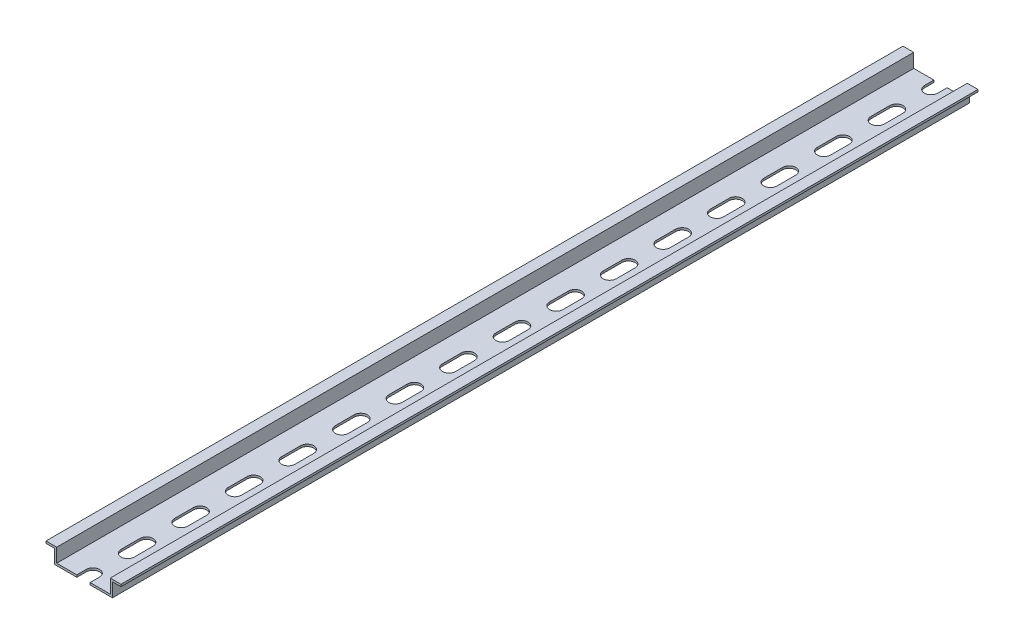
SolidWorks part; units mm, degrees
ref_plane "Front Plane" through (0, 0, 0) normal (0, 0, 1) x (1, 0, 0)
ref_plane "Top Plane" through (0, 0, 0) normal (0, 1, 0) x (1, 0, 0)
ref_plane "Right Plane" through (0, 0, 0) normal (1, 0, 0) x (0, 0, -1)
ref_plane "Plane4" through (0, -44.0251, 0) normal (0, 1, 0) x (1, 0, 0)
sketch "Sketch1" plane through (0, -44.0251, 0) normal (0, 1, 0) x (1, 0, 0)
  line L0 (139.3389, -100) -> (139.3389, 1900)
  line L1 (139.3389, 1900) -> (104.3389, 1900)
  line L2 (104.3389, 1900) -> (104.3389, -100)
  line L3 (104.3389, -100) -> (139.3389, -100)
extrude "Boss-Extrude1" add sketch "Sketch1" against normal blind 7.5
sketch "Sketch2" plane through (0, 0, -1900) normal (0, 0, -1) x (-1, 0, 0)
  line L0 (-134.3389, -44.0251) -> (-134.3389, -50.5251)
  line L1 (-134.3389, -50.5251) -> (-109.3389, -50.5251)
  line L2 (-109.3389, -50.5251) -> (-109.3389, -44.0251)
  line L3 (-109.3389, -44.0251) -> (-134.3389, -44.0251)
extrude "Cut-Extrude1" cut sketch "Sketch2" against normal through all
sketch "Sketch3" plane through (0, -51.5251, 0) normal (0, -1, 0) x (1, 0, 0)
  line L0 (118.7389, -1900) -> (124.9389, -1900)
  line L1 (124.9389, -1900) -> (124.9389, -1895.6)
  line L2 (118.7389, -1895.6) -> (118.7389, -1900)
  arc A0 (124.9389, -1895.6) -> (118.7389, -1895.6) centre (121.8389, -1895.6) ccw
extrude "Cut-Extrude2" cut sketch "Sketch3" against normal through all
sketch "Sketch4" plane through (0, 0, -1900) normal (0, 0, -1) x (-1, 0, 0)
  line L0 (-104.3389, -45.0251) -> (-108.3389, -45.0251)
  line L1 (-108.3389, -45.0251) -> (-108.3389, -51.5251)
  line L2 (-108.3389, -51.5251) -> (-104.3389, -51.5251)
  line L3 (-104.3389, -51.5251) -> (-104.3389, -45.0251)
extrude "Cut-Extrude3" cut sketch "Sketch4" against normal through all
sketch "Sketch5" plane through (0, 0, -1900) normal (0, 0, -1) x (-1, 0, 0)
  line L0 (-135.3389, -45.0251) -> (-139.3389, -45.0251)
  line L1 (-139.3389, -45.0251) -> (-139.3389, -51.5251)
  line L2 (-139.3389, -51.5251) -> (-135.3389, -51.5251)
  line L3 (-135.3389, -51.5251) -> (-135.3389, -45.0251)
extrude "Cut-Extrude4" cut sketch "Sketch5" against normal through all
sketch "Sketch6" plane through (0, -51.5251, 0) normal (0, -1, 0) x (1, 0, 0)
  line L0 (118.7389, 100) -> (118.7389, 95.6)
  line L1 (124.9389, 95.6) -> (124.9389, 100)
  line L2 (124.9389, 100) -> (118.7389, 100)
  arc A0 (118.7389, 95.6) -> (124.9389, 95.6) centre (121.8389, 95.6) ccw
extrude "Cut-Extrude5" cut sketch "Sketch6" against normal through all
sketch "Sketch7" plane through (0, -50.5251, 0) normal (0, 1, 0) x (-1, 0, 0)
  line L0 (-118.7389, -54.4) -> (-118.7389, -45.6)
  line L1 (-124.9389, -45.6) -> (-124.9389, -54.4)
  arc A0 (-118.7389, -45.6) -> (-124.9389, -45.6) centre (-121.8389, -45.6) ccw
  arc A1 (-124.9389, -54.4) -> (-118.7389, -54.4) centre (-121.8389, -54.4) ccw
extrude "Cut-Extrude6" cut sketch "Sketch7" against normal through all
sketch "Sketch8" plane through (0, -50.5251, 0) normal (0, 1, 0) x (-1, 0, 0)
  line L0 (-124.9389, 29.4) -> (-124.9389, 20.6)
  line L1 (-118.7389, 20.6) -> (-118.7389, 29.4)
  arc A0 (-118.7389, 29.4) -> (-124.9389, 29.4) centre (-121.8389, 29.4) ccw
  arc A1 (-124.9389, 20.6) -> (-118.7389, 20.6) centre (-121.8389, 20.6) ccw
extrude "Cut-Extrude7" cut sketch "Sketch8" against normal through all
sketch "Sketch9" plane through (0, -50.5251, 0) normal (0, 1, 0) x (-1, 0, 0)
  line L0 (-118.7389, -1829.4) -> (-118.7389, -1820.6)
  line L1 (-124.9389, -1820.6) -> (-124.9389, -1829.4)
  arc A0 (-118.7389, -1820.6) -> (-124.9389, -1820.6) centre (-121.8389, -1820.6) ccw
  arc A1 (-124.9389, -1829.4) -> (-118.7389, -1829.4) centre (-121.8389, -1829.4) ccw
extrude "Cut-Extrude8" cut sketch "Sketch9" against normal through all
sketch "Sketch10" plane through (0, -50.5251, 0) normal (0, 1, 0) x (-1, 0, 0)
  line L0 (-118.7389, -1529.4) -> (-118.7389, -1520.6)
  line L1 (-124.9389, -1520.6) -> (-124.9389, -1529.4)
  arc A0 (-118.7389, -1520.6) -> (-124.9389, -1520.6) centre (-121.8389, -1520.6) ccw
  arc A1 (-124.9389, -1529.4) -> (-118.7389, -1529.4) centre (-121.8389, -1529.4) ccw
extrude "Cut-Extrude9" cut sketch "Sketch10" against normal through all
sketch "Sketch11" plane through (0, -50.5251, 0) normal (0, 1, 0) x (-1, 0, 0)
  line L0 (-124.9389, -1120.6) -> (-124.9389, -1129.4)
  line L1 (-118.7389, -1129.4) -> (-118.7389, -1120.6)
  arc A0 (-124.9389, -1129.4) -> (-118.7389, -1129.4) centre (-121.8389, -1129.4) ccw
  arc A1 (-118.7389, -1120.6) -> (-124.9389, -1120.6) centre (-121.8389, -1120.6) ccw
extrude "Cut-Extrude10" cut sketch "Sketch11" against normal through all
sketch "Sketch12" plane through (0, -50.5251, 0) normal (0, 1, 0) x (-1, 0, 0)
  line L0 (-118.7389, -404.4) -> (-118.7389, -395.6)
  line L1 (-124.9389, -395.6) -> (-124.9389, -404.4)
  arc A0 (-124.9389, -404.4) -> (-118.7389, -404.4) centre (-121.8389, -404.4) ccw
  arc A1 (-118.7389, -395.6) -> (-124.9389, -395.6) centre (-121.8389, -395.6) ccw
extrude "Cut-Extrude11" cut sketch "Sketch12" against normal through all
sketch "Sketch13" plane through (0, -50.5251, 0) normal (0, 1, 0) x (-1, 0, 0)
  line L0 (-118.7389, -304.4) -> (-118.7389, -295.6)
  line L1 (-124.9389, -295.6) -> (-124.9389, -304.4)
  arc A0 (-118.7389, -295.6) -> (-124.9389, -295.6) centre (-121.8389, -295.6) ccw
  arc A1 (-124.9389, -304.4) -> (-118.7389, -304.4) centre (-121.8389, -304.4) ccw
extrude "Cut-Extrude12" cut sketch "Sketch13" against normal through all
sketch "Sketch14" plane through (0, -50.5251, 0) normal (0, 1, 0) x (-1, 0, 0)
  line L0 (-124.9389, -245.6) -> (-124.9389, -254.4)
  line L1 (-118.7389, -254.4) -> (-118.7389, -245.6)
  arc A0 (-124.9389, -254.4) -> (-118.7389, -254.4) centre (-121.8389, -254.4) ccw
  arc A1 (-118.7389, -245.6) -> (-124.9389, -245.6) centre (-121.8389, -245.6) ccw
extrude "Cut-Extrude13" cut sketch "Sketch14" against normal through all
sketch "Sketch15" plane through (0, -50.5251, 0) normal (0, 1, 0) x (-1, 0, 0)
  line L0 (-118.7389, 45.6) -> (-118.7389, 54.4)
  line L1 (-124.9389, 54.4) -> (-124.9389, 45.6)
  arc A0 (-118.7389, 54.4) -> (-124.9389, 54.4) centre (-121.8389, 54.4) ccw
  arc A1 (-124.9389, 45.6) -> (-118.7389, 45.6) centre (-121.8389, 45.6) ccw
extrude "Cut-Extrude14" cut sketch "Sketch15" against normal through all
sketch "Sketch16" plane through (0, -50.5251, 0) normal (0, 1, 0) x (-1, 0, 0)
  line L0 (-118.7389, -279.4) -> (-118.7389, -270.6)
  line L1 (-124.9389, -270.6) -> (-124.9389, -279.4)
  arc A0 (-124.9389, -279.4) -> (-118.7389, -279.4) centre (-121.8389, -279.4) ccw
  arc A1 (-118.7389, -270.6) -> (-124.9389, -270.6) centre (-121.8389, -270.6) ccw
extrude "Cut-Extrude15" cut sketch "Sketch16" against normal through all
sketch "Sketch17" plane through (0, -50.5251, 0) normal (0, 1, 0) x (-1, 0, 0)
  line L0 (-124.9389, -920.6) -> (-124.9389, -929.4)
  line L1 (-118.7389, -929.4) -> (-118.7389, -920.6)
  arc A0 (-124.9389, -929.4) -> (-118.7389, -929.4) centre (-121.8389, -929.4) ccw
  arc A1 (-118.7389, -920.6) -> (-124.9389, -920.6) centre (-121.8389, -920.6) ccw
extrude "Cut-Extrude16" cut sketch "Sketch17" against normal through all
sketch "Sketch18" plane through (0, -50.5251, 0) normal (0, 1, 0) x (-1, 0, 0)
  line L0 (-118.7389, -1504.4) -> (-118.7389, -1495.6)
  line L1 (-124.9389, -1495.6) -> (-124.9389, -1504.4)
  arc A0 (-118.7389, -1495.6) -> (-124.9389, -1495.6) centre (-121.8389, -1495.6) ccw
  arc A1 (-124.9389, -1504.4) -> (-118.7389, -1504.4) centre (-121.8389, -1504.4) ccw
extrude "Cut-Extrude17" cut sketch "Sketch18" against normal through all
sketch "Sketch19" plane through (0, -50.5251, 0) normal (0, 1, 0) x (-1, 0, 0)
  line L0 (-124.9389, -970.6) -> (-124.9389, -979.4)
  line L1 (-118.7389, -979.4) -> (-118.7389, -970.6)
  arc A0 (-124.9389, -979.4) -> (-118.7389, -979.4) centre (-121.8389, -979.4) ccw
  arc A1 (-118.7389, -970.6) -> (-124.9389, -970.6) centre (-121.8389, -970.6) ccw
extrude "Cut-Extrude18" cut sketch "Sketch19" against normal through all
sketch "Sketch20" plane through (0, -50.5251, 0) normal (0, 1, 0) x (-1, 0, 0)
  line L0 (-118.7389, -204.4) -> (-118.7389, -195.6)
  line L1 (-124.9389, -195.6) -> (-124.9389, -204.4)
  arc A0 (-124.9389, -204.4) -> (-118.7389, -204.4) centre (-121.8389, -204.4) ccw
  arc A1 (-118.7389, -195.6) -> (-124.9389, -195.6) centre (-121.8389, -195.6) ccw
extrude "Cut-Extrude19" cut sketch "Sketch20" against normal through all
sketch "Sketch21" plane through (0, -50.5251, 0) normal (0, 1, 0) x (-1, 0, 0)
  line L0 (-118.7389, -79.4) -> (-118.7389, -70.6)
  line L1 (-124.9389, -70.6) -> (-124.9389, -79.4)
  arc A0 (-118.7389, -70.6) -> (-124.9389, -70.6) centre (-121.8389, -70.6) ccw
  arc A1 (-124.9389, -79.4) -> (-118.7389, -79.4) centre (-121.8389, -79.4) ccw
extrude "Cut-Extrude20" cut sketch "Sketch21" against normal through all
sketch "Sketch22" plane through (0, -50.5251, 0) normal (0, 1, 0) x (-1, 0, 0)
  line L0 (-118.7389, -1379.4) -> (-118.7389, -1370.6)
  line L1 (-124.9389, -1370.6) -> (-124.9389, -1379.4)
  arc A0 (-118.7389, -1370.6) -> (-124.9389, -1370.6) centre (-121.8389, -1370.6) ccw
  arc A1 (-124.9389, -1379.4) -> (-118.7389, -1379.4) centre (-121.8389, -1379.4) ccw
extrude "Cut-Extrude21" cut sketch "Sketch22" against normal through all
sketch "Sketch23" plane through (0, -50.5251, 0) normal (0, 1, 0) x (-1, 0, 0)
  line L0 (-118.7389, -1604.4) -> (-118.7389, -1595.6)
  line L1 (-124.9389, -1595.6) -> (-124.9389, -1604.4)
  arc A0 (-124.9389, -1604.4) -> (-118.7389, -1604.4) centre (-121.8389, -1604.4) ccw
  arc A1 (-118.7389, -1595.6) -> (-124.9389, -1595.6) centre (-121.8389, -1595.6) ccw
extrude "Cut-Extrude22" cut sketch "Sketch23" against normal through all
sketch "Sketch24" plane through (0, -50.5251, 0) normal (0, 1, 0) x (-1, 0, 0)
  line L0 (-118.7389, -1254.4) -> (-118.7389, -1245.6)
  line L1 (-124.9389, -1245.6) -> (-124.9389, -1254.4)
  arc A0 (-124.9389, -1254.4) -> (-118.7389, -1254.4) centre (-121.8389, -1254.4) ccw
  arc A1 (-118.7389, -1245.6) -> (-124.9389, -1245.6) centre (-121.8389, -1245.6) ccw
extrude "Cut-Extrude23" cut sketch "Sketch24" against normal through all
sketch "Sketch25" plane through (0, -50.5251, 0) normal (0, 1, 0) x (-1, 0, 0)
  line L0 (-118.7389, -154.4) -> (-118.7389, -145.6)
  line L1 (-124.9389, -145.6) -> (-124.9389, -154.4)
  arc A0 (-118.7389, -145.6) -> (-124.9389, -145.6) centre (-121.8389, -145.6) ccw
  arc A1 (-124.9389, -154.4) -> (-118.7389, -154.4) centre (-121.8389, -154.4) ccw
extrude "Cut-Extrude24" cut sketch "Sketch25" against normal through all
sketch "Sketch26" plane through (0, -50.5251, 0) normal (0, 1, 0) x (-1, 0, 0)
  line L0 (-118.7389, -1554.4) -> (-118.7389, -1545.6)
  line L1 (-124.9389, -1545.6) -> (-124.9389, -1554.4)
  arc A0 (-118.7389, -1545.6) -> (-124.9389, -1545.6) centre (-121.8389, -1545.6) ccw
  arc A1 (-124.9389, -1554.4) -> (-118.7389, -1554.4) centre (-121.8389, -1554.4) ccw
extrude "Cut-Extrude25" cut sketch "Sketch26" against normal through all
sketch "Sketch27" plane through (0, -50.5251, 0) normal (0, 1, 0) x (-1, 0, 0)
  line L0 (-124.9389, -1020.6) -> (-124.9389, -1029.4)
  line L1 (-118.7389, -1029.4) -> (-118.7389, -1020.6)
  arc A0 (-124.9389, -1029.4) -> (-118.7389, -1029.4) centre (-121.8389, -1029.4) ccw
  arc A1 (-118.7389, -1020.6) -> (-124.9389, -1020.6) centre (-121.8389, -1020.6) ccw
extrude "Cut-Extrude26" cut sketch "Sketch27" against normal through all
sketch "Sketch28" plane through (0, -50.5251, 0) normal (0, 1, 0) x (-1, 0, 0)
  line L0 (-118.7389, -1629.4) -> (-118.7389, -1620.6)
  line L1 (-124.9389, -1620.6) -> (-124.9389, -1629.4)
  arc A0 (-124.9389, -1629.4) -> (-118.7389, -1629.4) centre (-121.8389, -1629.4) ccw
  arc A1 (-118.7389, -1620.6) -> (-124.9389, -1620.6) centre (-121.8389, -1620.6) ccw
extrude "Cut-Extrude27" cut sketch "Sketch28" against normal through all
sketch "Sketch29" plane through (0, -50.5251, 0) normal (0, 1, 0) x (-1, 0, 0)
  line L0 (-118.7389, -529.4) -> (-118.7389, -520.6)
  line L1 (-124.9389, -520.6) -> (-124.9389, -529.4)
  arc A0 (-118.7389, -520.6) -> (-124.9389, -520.6) centre (-121.8389, -520.6) ccw
  arc A1 (-124.9389, -529.4) -> (-118.7389, -529.4) centre (-121.8389, -529.4) ccw
extrude "Cut-Extrude28" cut sketch "Sketch29" against normal through all
sketch "Sketch30" plane through (0, -50.5251, 0) normal (0, 1, 0) x (-1, 0, 0)
  line L0 (-118.7389, -1104.4) -> (-118.7389, -1095.6)
  line L1 (-124.9389, -1095.6) -> (-124.9389, -1104.4)
  arc A0 (-118.7389, -1095.6) -> (-124.9389, -1095.6) centre (-121.8389, -1095.6) ccw
  arc A1 (-124.9389, -1104.4) -> (-118.7389, -1104.4) centre (-121.8389, -1104.4) ccw
extrude "Cut-Extrude29" cut sketch "Sketch30" against normal through all
sketch "Sketch31" plane through (0, -50.5251, 0) normal (0, 1, 0) x (-1, 0, 0)
  line L0 (-118.7389, -429.4) -> (-118.7389, -420.6)
  line L1 (-124.9389, -420.6) -> (-124.9389, -429.4)
  arc A0 (-118.7389, -420.6) -> (-124.9389, -420.6) centre (-121.8389, -420.6) ccw
  arc A1 (-124.9389, -429.4) -> (-118.7389, -429.4) centre (-121.8389, -429.4) ccw
extrude "Cut-Extrude30" cut sketch "Sketch31" against normal through all
sketch "Sketch32" plane through (0, -50.5251, 0) normal (0, 1, 0) x (-1, 0, 0)
  line L0 (-118.7389, -829.4) -> (-118.7389, -820.6)
  line L1 (-124.9389, -820.6) -> (-124.9389, -829.4)
  arc A0 (-124.9389, -829.4) -> (-118.7389, -829.4) centre (-121.8389, -829.4) ccw
  arc A1 (-118.7389, -820.6) -> (-124.9389, -820.6) centre (-121.8389, -820.6) ccw
extrude "Cut-Extrude31" cut sketch "Sketch32" against normal through all
sketch "Sketch33" plane through (0, -50.5251, 0) normal (0, 1, 0) x (-1, 0, 0)
  line L0 (-124.9389, -870.6) -> (-124.9389, -879.4)
  line L1 (-118.7389, -879.4) -> (-118.7389, -870.6)
  arc A0 (-118.7389, -870.6) -> (-124.9389, -870.6) centre (-121.8389, -870.6) ccw
  arc A1 (-124.9389, -879.4) -> (-118.7389, -879.4) centre (-121.8389, -879.4) ccw
extrude "Cut-Extrude32" cut sketch "Sketch33" against normal through all
sketch "Sketch34" plane through (0, -50.5251, 0) normal (0, 1, 0) x (-1, 0, 0)
  line L0 (-118.7389, -4.4) -> (-118.7389, 4.4)
  line L1 (-124.9389, 4.4) -> (-124.9389, -4.4)
  arc A0 (-118.7389, 4.4) -> (-124.9389, 4.4) centre (-121.8389, 4.4) ccw
  arc A1 (-124.9389, -4.4) -> (-118.7389, -4.4) centre (-121.8389, -4.4) ccw
extrude "Cut-Extrude33" cut sketch "Sketch34" against normal through all
sketch "Sketch35" plane through (0, -50.5251, 0) normal (0, 1, 0) x (-1, 0, 0)
  line L0 (-118.7389, -104.4) -> (-118.7389, -95.6)
  line L1 (-124.9389, -95.6) -> (-124.9389, -104.4)
  arc A0 (-118.7389, -95.6) -> (-124.9389, -95.6) centre (-121.8389, -95.6) ccw
  arc A1 (-124.9389, -104.4) -> (-118.7389, -104.4) centre (-121.8389, -104.4) ccw
extrude "Cut-Extrude34" cut sketch "Sketch35" against normal through all
sketch "Sketch36" plane through (0, -50.5251, 0) normal (0, 1, 0) x (-1, 0, 0)
  line L0 (-118.7389, -754.4) -> (-118.7389, -745.6)
  line L1 (-124.9389, -745.6) -> (-124.9389, -754.4)
  arc A0 (-124.9389, -754.4) -> (-118.7389, -754.4) centre (-121.8389, -754.4) ccw
  arc A1 (-118.7389, -745.6) -> (-124.9389, -745.6) centre (-121.8389, -745.6) ccw
extrude "Cut-Extrude35" cut sketch "Sketch36" against normal through all
sketch "Sketch37" plane through (0, -50.5251, 0) normal (0, 1, 0) x (-1, 0, 0)
  line L0 (-124.9389, -1570.6) -> (-124.9389, -1579.4)
  line L1 (-118.7389, -1579.4) -> (-118.7389, -1570.6)
  arc A0 (-124.9389, -1579.4) -> (-118.7389, -1579.4) centre (-121.8389, -1579.4) ccw
  arc A1 (-118.7389, -1570.6) -> (-124.9389, -1570.6) centre (-121.8389, -1570.6) ccw
extrude "Cut-Extrude36" cut sketch "Sketch37" against normal through all
sketch "Sketch38" plane through (0, -50.5251, 0) normal (0, 1, 0) x (-1, 0, 0)
  line L0 (-118.7389, -1404.4) -> (-118.7389, -1395.6)
  line L1 (-124.9389, -1395.6) -> (-124.9389, -1404.4)
  arc A0 (-118.7389, -1395.6) -> (-124.9389, -1395.6) centre (-121.8389, -1395.6) ccw
  arc A1 (-124.9389, -1404.4) -> (-118.7389, -1404.4) centre (-121.8389, -1404.4) ccw
extrude "Cut-Extrude37" cut sketch "Sketch38" against normal through all
sketch "Sketch39" plane through (0, -50.5251, 0) normal (0, 1, 0) x (-1, 0, 0)
  line L0 (-118.7389, -1329.4) -> (-118.7389, -1320.6)
  line L1 (-124.9389, -1320.6) -> (-124.9389, -1329.4)
  arc A0 (-124.9389, -1329.4) -> (-118.7389, -1329.4) centre (-121.8389, -1329.4) ccw
  arc A1 (-118.7389, -1320.6) -> (-124.9389, -1320.6) centre (-121.8389, -1320.6) ccw
extrude "Cut-Extrude38" cut sketch "Sketch39" against normal through all
sketch "Sketch40" plane through (0, -50.5251, 0) normal (0, 1, 0) x (-1, 0, 0)
  line L0 (-118.7389, -904.4) -> (-118.7389, -895.6)
  line L1 (-124.9389, -895.6) -> (-124.9389, -904.4)
  arc A0 (-124.9389, -904.4) -> (-118.7389, -904.4) centre (-121.8389, -904.4) ccw
  arc A1 (-118.7389, -895.6) -> (-124.9389, -895.6) centre (-121.8389, -895.6) ccw
extrude "Cut-Extrude39" cut sketch "Sketch40" against normal through all
sketch "Sketch41" plane through (0, -50.5251, 0) normal (0, 1, 0) x (-1, 0, 0)
  line L0 (-118.7389, -1854.4) -> (-118.7389, -1845.6)
  line L1 (-124.9389, -1845.6) -> (-124.9389, -1854.4)
  arc A0 (-118.7389, -1845.6) -> (-124.9389, -1845.6) centre (-121.8389, -1845.6) ccw
  arc A1 (-124.9389, -1854.4) -> (-118.7389, -1854.4) centre (-121.8389, -1854.4) ccw
extrude "Cut-Extrude40" cut sketch "Sketch41" against normal through all
sketch "Sketch42" plane through (0, -50.5251, 0) normal (0, 1, 0) x (-1, 0, 0)
  line L0 (-124.9389, -670.6) -> (-124.9389, -679.4)
  line L1 (-118.7389, -679.4) -> (-118.7389, -670.6)
  arc A0 (-118.7389, -670.6) -> (-124.9389, -670.6) centre (-121.8389, -670.6) ccw
  arc A1 (-124.9389, -679.4) -> (-118.7389, -679.4) centre (-121.8389, -679.4) ccw
extrude "Cut-Extrude41" cut sketch "Sketch42" against normal through all
sketch "Sketch43" plane through (0, -50.5251, 0) normal (0, 1, 0) x (-1, 0, 0)
  line L0 (-118.7389, -1804.4) -> (-118.7389, -1795.6)
  line L1 (-124.9389, -1795.6) -> (-124.9389, -1804.4)
  arc A0 (-118.7389, -1795.6) -> (-124.9389, -1795.6) centre (-121.8389, -1795.6) ccw
  arc A1 (-124.9389, -1804.4) -> (-118.7389, -1804.4) centre (-121.8389, -1804.4) ccw
extrude "Cut-Extrude42" cut sketch "Sketch43" against normal through all
sketch "Sketch44" plane through (0, -50.5251, 0) normal (0, 1, 0) x (-1, 0, 0)
  line L0 (-118.7389, -229.4) -> (-118.7389, -220.6)
  line L1 (-124.9389, -220.6) -> (-124.9389, -229.4)
  arc A0 (-118.7389, -220.6) -> (-124.9389, -220.6) centre (-121.8389, -220.6) ccw
  arc A1 (-124.9389, -229.4) -> (-118.7389, -229.4) centre (-121.8389, -229.4) ccw
extrude "Cut-Extrude43" cut sketch "Sketch44" against normal through all
sketch "Sketch45" plane through (0, -50.5251, 0) normal (0, 1, 0) x (-1, 0, 0)
  line L0 (-118.7389, -29.4) -> (-118.7389, -20.6)
  line L1 (-124.9389, -20.6) -> (-124.9389, -29.4)
  arc A0 (-118.7389, -20.6) -> (-124.9389, -20.6) centre (-121.8389, -20.6) ccw
  arc A1 (-124.9389, -29.4) -> (-118.7389, -29.4) centre (-121.8389, -29.4) ccw
extrude "Cut-Extrude44" cut sketch "Sketch45" against normal through all
sketch "Sketch46" plane through (0, -50.5251, 0) normal (0, 1, 0) x (-1, 0, 0)
  line L0 (-124.9389, -1445.6) -> (-124.9389, -1454.4)
  line L1 (-118.7389, -1454.4) -> (-118.7389, -1445.6)
  arc A0 (-124.9389, -1454.4) -> (-118.7389, -1454.4) centre (-121.8389, -1454.4) ccw
  arc A1 (-118.7389, -1445.6) -> (-124.9389, -1445.6) centre (-121.8389, -1445.6) ccw
extrude "Cut-Extrude45" cut sketch "Sketch46" against normal through all
sketch "Sketch47" plane through (0, -50.5251, 0) normal (0, 1, 0) x (-1, 0, 0)
  line L0 (-118.7389, -1054.4) -> (-118.7389, -1045.6)
  line L1 (-124.9389, -1045.6) -> (-124.9389, -1054.4)
  arc A0 (-118.7389, -1045.6) -> (-124.9389, -1045.6) centre (-121.8389, -1045.6) ccw
  arc A1 (-124.9389, -1054.4) -> (-118.7389, -1054.4) centre (-121.8389, -1054.4) ccw
extrude "Cut-Extrude46" cut sketch "Sketch47" against normal through all
sketch "Sketch48" plane through (0, -50.5251, 0) normal (0, 1, 0) x (-1, 0, 0)
  line L0 (-124.9389, -795.6) -> (-124.9389, -804.4)
  line L1 (-118.7389, -804.4) -> (-118.7389, -795.6)
  arc A0 (-118.7389, -795.6) -> (-124.9389, -795.6) centre (-121.8389, -795.6) ccw
  arc A1 (-124.9389, -804.4) -> (-118.7389, -804.4) centre (-121.8389, -804.4) ccw
extrude "Cut-Extrude47" cut sketch "Sketch48" against normal through all
sketch "Sketch49" plane through (0, -50.5251, 0) normal (0, 1, 0) x (-1, 0, 0)
  line L0 (-118.7389, 70.6) -> (-118.7389, 79.4)
  line L1 (-124.9389, 79.4) -> (-124.9389, 70.6)
  arc A0 (-118.7389, 79.4) -> (-124.9389, 79.4) centre (-121.8389, 79.4) ccw
  arc A1 (-124.9389, 70.6) -> (-118.7389, 70.6) centre (-121.8389, 70.6) ccw
extrude "Cut-Extrude48" cut sketch "Sketch49" against normal through all
sketch "Sketch50" plane through (0, -50.5251, 0) normal (0, 1, 0) x (-1, 0, 0)
  line L0 (-118.7389, -579.4) -> (-118.7389, -570.6)
  line L1 (-124.9389, -570.6) -> (-124.9389, -579.4)
  arc A0 (-118.7389, -570.6) -> (-124.9389, -570.6) centre (-121.8389, -570.6) ccw
  arc A1 (-124.9389, -579.4) -> (-118.7389, -579.4) centre (-121.8389, -579.4) ccw
extrude "Cut-Extrude49" cut sketch "Sketch50" against normal through all
sketch "Sketch51" plane through (0, -50.5251, 0) normal (0, 1, 0) x (-1, 0, 0)
  line L0 (-118.7389, -1679.4) -> (-118.7389, -1670.6)
  line L1 (-124.9389, -1670.6) -> (-124.9389, -1679.4)
  arc A0 (-118.7389, -1670.6) -> (-124.9389, -1670.6) centre (-121.8389, -1670.6) ccw
  arc A1 (-124.9389, -1679.4) -> (-118.7389, -1679.4) centre (-121.8389, -1679.4) ccw
extrude "Cut-Extrude50" cut sketch "Sketch51" against normal through all
sketch "Sketch52" plane through (0, -50.5251, 0) normal (0, 1, 0) x (-1, 0, 0)
  line L0 (-124.9389, -1470.6) -> (-124.9389, -1479.4)
  line L1 (-118.7389, -1479.4) -> (-118.7389, -1470.6)
  arc A0 (-124.9389, -1479.4) -> (-118.7389, -1479.4) centre (-121.8389, -1479.4) ccw
  arc A1 (-118.7389, -1470.6) -> (-124.9389, -1470.6) centre (-121.8389, -1470.6) ccw
extrude "Cut-Extrude51" cut sketch "Sketch52" against normal through all
sketch "Sketch53" plane through (0, -50.5251, 0) normal (0, 1, 0) x (-1, 0, 0)
  line L0 (-118.7389, -454.4) -> (-118.7389, -445.6)
  line L1 (-124.9389, -445.6) -> (-124.9389, -454.4)
  arc A0 (-118.7389, -445.6) -> (-124.9389, -445.6) centre (-121.8389, -445.6) ccw
  arc A1 (-124.9389, -454.4) -> (-118.7389, -454.4) centre (-121.8389, -454.4) ccw
extrude "Cut-Extrude52" cut sketch "Sketch53" against normal through all
sketch "Sketch54" plane through (0, -50.5251, 0) normal (0, 1, 0) x (-1, 0, 0)
  line L0 (-124.9389, -995.6) -> (-124.9389, -1004.4)
  line L1 (-118.7389, -1004.4) -> (-118.7389, -995.6)
  arc A0 (-118.7389, -995.6) -> (-124.9389, -995.6) centre (-121.8389, -995.6) ccw
  arc A1 (-124.9389, -1004.4) -> (-118.7389, -1004.4) centre (-121.8389, -1004.4) ccw
extrude "Cut-Extrude53" cut sketch "Sketch54" against normal through all
sketch "Sketch55" plane through (0, -50.5251, 0) normal (0, 1, 0) x (-1, 0, 0)
  line L0 (-118.7389, -1279.4) -> (-118.7389, -1270.6)
  line L1 (-124.9389, -1270.6) -> (-124.9389, -1279.4)
  arc A0 (-118.7389, -1270.6) -> (-124.9389, -1270.6) centre (-121.8389, -1270.6) ccw
  arc A1 (-124.9389, -1279.4) -> (-118.7389, -1279.4) centre (-121.8389, -1279.4) ccw
extrude "Cut-Extrude54" cut sketch "Sketch55" against normal through all
sketch "Sketch56" plane through (0, -50.5251, 0) normal (0, 1, 0) x (-1, 0, 0)
  line L0 (-118.7389, -729.4) -> (-118.7389, -720.6)
  line L1 (-124.9389, -720.6) -> (-124.9389, -729.4)
  arc A0 (-118.7389, -720.6) -> (-124.9389, -720.6) centre (-121.8389, -720.6) ccw
  arc A1 (-124.9389, -729.4) -> (-118.7389, -729.4) centre (-121.8389, -729.4) ccw
extrude "Cut-Extrude55" cut sketch "Sketch56" against normal through all
sketch "Sketch57" plane through (0, -50.5251, 0) normal (0, 1, 0) x (-1, 0, 0)
  line L0 (-124.9389, -645.6) -> (-124.9389, -654.4)
  line L1 (-118.7389, -654.4) -> (-118.7389, -645.6)
  arc A0 (-124.9389, -654.4) -> (-118.7389, -654.4) centre (-121.8389, -654.4) ccw
  arc A1 (-118.7389, -645.6) -> (-124.9389, -645.6) centre (-121.8389, -645.6) ccw
extrude "Cut-Extrude56" cut sketch "Sketch57" against normal through all
sketch "Sketch58" plane through (0, -50.5251, 0) normal (0, 1, 0) x (-1, 0, 0)
  line L0 (-124.9389, -1645.6) -> (-124.9389, -1654.4)
  line L1 (-118.7389, -1654.4) -> (-118.7389, -1645.6)
  arc A0 (-124.9389, -1654.4) -> (-118.7389, -1654.4) centre (-121.8389, -1654.4) ccw
  arc A1 (-118.7389, -1645.6) -> (-124.9389, -1645.6) centre (-121.8389, -1645.6) ccw
extrude "Cut-Extrude57" cut sketch "Sketch58" against normal through all
sketch "Sketch59" plane through (0, -50.5251, 0) normal (0, 1, 0) x (-1, 0, 0)
  line L0 (-118.7389, -479.4) -> (-118.7389, -470.6)
  line L1 (-124.9389, -470.6) -> (-124.9389, -479.4)
  arc A0 (-118.7389, -470.6) -> (-124.9389, -470.6) centre (-121.8389, -470.6) ccw
  arc A1 (-124.9389, -479.4) -> (-118.7389, -479.4) centre (-121.8389, -479.4) ccw
extrude "Cut-Extrude58" cut sketch "Sketch59" against normal through all
sketch "Sketch60" plane through (0, -50.5251, 0) normal (0, 1, 0) x (-1, 0, 0)
  line L0 (-124.9389, -1770.6) -> (-124.9389, -1779.4)
  line L1 (-118.7389, -1779.4) -> (-118.7389, -1770.6)
  arc A0 (-118.7389, -1770.6) -> (-124.9389, -1770.6) centre (-121.8389, -1770.6) ccw
  arc A1 (-124.9389, -1779.4) -> (-118.7389, -1779.4) centre (-121.8389, -1779.4) ccw
extrude "Cut-Extrude59" cut sketch "Sketch60" against normal through all
sketch "Sketch61" plane through (0, -50.5251, 0) normal (0, 1, 0) x (-1, 0, 0)
  line L0 (-118.7389, -704.4) -> (-118.7389, -695.6)
  line L1 (-124.9389, -695.6) -> (-124.9389, -704.4)
  arc A0 (-118.7389, -695.6) -> (-124.9389, -695.6) centre (-121.8389, -695.6) ccw
  arc A1 (-124.9389, -704.4) -> (-118.7389, -704.4) centre (-121.8389, -704.4) ccw
extrude "Cut-Extrude60" cut sketch "Sketch61" against normal through all
sketch "Sketch62" plane through (0, -50.5251, 0) normal (0, 1, 0) x (-1, 0, 0)
  line L0 (-118.7389, -854.4) -> (-118.7389, -845.6)
  line L1 (-124.9389, -845.6) -> (-124.9389, -854.4)
  arc A0 (-118.7389, -845.6) -> (-124.9389, -845.6) centre (-121.8389, -845.6) ccw
  arc A1 (-124.9389, -854.4) -> (-118.7389, -854.4) centre (-121.8389, -854.4) ccw
extrude "Cut-Extrude61" cut sketch "Sketch62" against normal through all
sketch "Sketch63" plane through (0, -50.5251, 0) normal (0, 1, 0) x (-1, 0, 0)
  line L0 (-118.7389, -1179.4) -> (-118.7389, -1170.6)
  line L1 (-124.9389, -1170.6) -> (-124.9389, -1179.4)
  arc A0 (-118.7389, -1170.6) -> (-124.9389, -1170.6) centre (-121.8389, -1170.6) ccw
  arc A1 (-124.9389, -1179.4) -> (-118.7389, -1179.4) centre (-121.8389, -1179.4) ccw
extrude "Cut-Extrude62" cut sketch "Sketch63" against normal through all
sketch "Sketch64" plane through (0, -50.5251, 0) normal (0, 1, 0) x (-1, 0, 0)
  line L0 (-124.9389, -1720.6) -> (-124.9389, -1729.4)
  line L1 (-118.7389, -1729.4) -> (-118.7389, -1720.6)
  arc A0 (-124.9389, -1729.4) -> (-118.7389, -1729.4) centre (-121.8389, -1729.4) ccw
  arc A1 (-118.7389, -1720.6) -> (-124.9389, -1720.6) centre (-121.8389, -1720.6) ccw
extrude "Cut-Extrude63" cut sketch "Sketch64" against normal through all
sketch "Sketch65" plane through (0, -50.5251, 0) normal (0, 1, 0) x (-1, 0, 0)
  line L0 (-124.9389, -1195.6) -> (-124.9389, -1204.4)
  line L1 (-118.7389, -1204.4) -> (-118.7389, -1195.6)
  arc A0 (-118.7389, -1195.6) -> (-124.9389, -1195.6) centre (-121.8389, -1195.6) ccw
  arc A1 (-124.9389, -1204.4) -> (-118.7389, -1204.4) centre (-121.8389, -1204.4) ccw
extrude "Cut-Extrude64" cut sketch "Sketch65" against normal through all
sketch "Sketch66" plane through (0, -50.5251, 0) normal (0, 1, 0) x (-1, 0, 0)
  line L0 (-118.7389, -1704.4) -> (-118.7389, -1695.6)
  line L1 (-124.9389, -1695.6) -> (-124.9389, -1704.4)
  arc A0 (-118.7389, -1695.6) -> (-124.9389, -1695.6) centre (-121.8389, -1695.6) ccw
  arc A1 (-124.9389, -1704.4) -> (-118.7389, -1704.4) centre (-121.8389, -1704.4) ccw
extrude "Cut-Extrude65" cut sketch "Sketch66" against normal through all
sketch "Sketch67" plane through (0, -50.5251, 0) normal (0, 1, 0) x (-1, 0, 0)
  line L0 (-118.7389, -329.4) -> (-118.7389, -320.6)
  line L1 (-124.9389, -320.6) -> (-124.9389, -329.4)
  arc A0 (-118.7389, -320.6) -> (-124.9389, -320.6) centre (-121.8389, -320.6) ccw
  arc A1 (-124.9389, -329.4) -> (-118.7389, -329.4) centre (-121.8389, -329.4) ccw
extrude "Cut-Extrude66" cut sketch "Sketch67" against normal through all
sketch "Sketch68" plane through (0, -50.5251, 0) normal (0, 1, 0) x (-1, 0, 0)
  line L0 (-118.7389, -554.4) -> (-118.7389, -545.6)
  line L1 (-124.9389, -545.6) -> (-124.9389, -554.4)
  arc A0 (-118.7389, -545.6) -> (-124.9389, -545.6) centre (-121.8389, -545.6) ccw
  arc A1 (-124.9389, -554.4) -> (-118.7389, -554.4) centre (-121.8389, -554.4) ccw
extrude "Cut-Extrude67" cut sketch "Sketch68" against normal through all
sketch "Sketch69" plane through (0, -50.5251, 0) normal (0, 1, 0) x (-1, 0, 0)
  line L0 (-118.7389, -379.4) -> (-118.7389, -370.6)
  line L1 (-124.9389, -370.6) -> (-124.9389, -379.4)
  arc A0 (-124.9389, -379.4) -> (-118.7389, -379.4) centre (-121.8389, -379.4) ccw
  arc A1 (-118.7389, -370.6) -> (-124.9389, -370.6) centre (-121.8389, -370.6) ccw
extrude "Cut-Extrude68" cut sketch "Sketch69" against normal through all
sketch "Sketch70" plane through (0, -50.5251, 0) normal (0, 1, 0) x (-1, 0, 0)
  line L0 (-118.7389, -1229.4) -> (-118.7389, -1220.6)
  line L1 (-124.9389, -1220.6) -> (-124.9389, -1229.4)
  arc A0 (-118.7389, -1220.6) -> (-124.9389, -1220.6) centre (-121.8389, -1220.6) ccw
  arc A1 (-124.9389, -1229.4) -> (-118.7389, -1229.4) centre (-121.8389, -1229.4) ccw
extrude "Cut-Extrude69" cut sketch "Sketch70" against normal through all
sketch "Sketch71" plane through (0, -50.5251, 0) normal (0, 1, 0) x (-1, 0, 0)
  line L0 (-118.7389, -629.4) -> (-118.7389, -620.6)
  line L1 (-124.9389, -620.6) -> (-124.9389, -629.4)
  arc A0 (-118.7389, -620.6) -> (-124.9389, -620.6) centre (-121.8389, -620.6) ccw
  arc A1 (-124.9389, -629.4) -> (-118.7389, -629.4) centre (-121.8389, -629.4) ccw
extrude "Cut-Extrude70" cut sketch "Sketch71" against normal through all
sketch "Sketch72" plane through (0, -50.5251, 0) normal (0, 1, 0) x (-1, 0, 0)
  line L0 (-118.7389, -604.4) -> (-118.7389, -595.6)
  line L1 (-124.9389, -595.6) -> (-124.9389, -604.4)
  arc A0 (-118.7389, -595.6) -> (-124.9389, -595.6) centre (-121.8389, -595.6) ccw
  arc A1 (-124.9389, -604.4) -> (-118.7389, -604.4) centre (-121.8389, -604.4) ccw
extrude "Cut-Extrude71" cut sketch "Sketch72" against normal through all
sketch "Sketch73" plane through (0, -50.5251, 0) normal (0, 1, 0) x (-1, 0, 0)
  line L0 (-124.9389, -1745.6) -> (-124.9389, -1754.4)
  line L1 (-118.7389, -1754.4) -> (-118.7389, -1745.6)
  arc A0 (-124.9389, -1754.4) -> (-118.7389, -1754.4) centre (-121.8389, -1754.4) ccw
  arc A1 (-118.7389, -1745.6) -> (-124.9389, -1745.6) centre (-121.8389, -1745.6) ccw
extrude "Cut-Extrude72" cut sketch "Sketch73" against normal through all
sketch "Sketch74" plane through (0, -50.5251, 0) normal (0, 1, 0) x (-1, 0, 0)
  line L0 (-124.9389, -1420.6) -> (-124.9389, -1429.4)
  line L1 (-118.7389, -1429.4) -> (-118.7389, -1420.6)
  arc A0 (-124.9389, -1429.4) -> (-118.7389, -1429.4) centre (-121.8389, -1429.4) ccw
  arc A1 (-118.7389, -1420.6) -> (-124.9389, -1420.6) centre (-121.8389, -1420.6) ccw
extrude "Cut-Extrude73" cut sketch "Sketch74" against normal through all
sketch "Sketch75" plane through (0, -50.5251, 0) normal (0, 1, 0) x (-1, 0, 0)
  line L0 (-124.9389, -1295.6) -> (-124.9389, -1304.4)
  line L1 (-118.7389, -1304.4) -> (-118.7389, -1295.6)
  arc A0 (-118.7389, -1295.6) -> (-124.9389, -1295.6) centre (-121.8389, -1295.6) ccw
  arc A1 (-124.9389, -1304.4) -> (-118.7389, -1304.4) centre (-121.8389, -1304.4) ccw
extrude "Cut-Extrude74" cut sketch "Sketch75" against normal through all
sketch "Sketch76" plane through (0, -50.5251, 0) normal (0, 1, 0) x (-1, 0, 0)
  line L0 (-118.7389, -179.4) -> (-118.7389, -170.6)
  line L1 (-124.9389, -170.6) -> (-124.9389, -179.4)
  arc A0 (-118.7389, -170.6) -> (-124.9389, -170.6) centre (-121.8389, -170.6) ccw
  arc A1 (-124.9389, -179.4) -> (-118.7389, -179.4) centre (-121.8389, -179.4) ccw
extrude "Cut-Extrude75" cut sketch "Sketch76" against normal through all
sketch "Sketch77" plane through (0, -50.5251, 0) normal (0, 1, 0) x (-1, 0, 0)
  line L0 (-124.9389, -345.6) -> (-124.9389, -354.4)
  line L1 (-118.7389, -354.4) -> (-118.7389, -345.6)
  arc A0 (-118.7389, -345.6) -> (-124.9389, -345.6) centre (-121.8389, -345.6) ccw
  arc A1 (-124.9389, -354.4) -> (-118.7389, -354.4) centre (-121.8389, -354.4) ccw
extrude "Cut-Extrude76" cut sketch "Sketch77" against normal through all
sketch "Sketch78" plane through (0, -50.5251, 0) normal (0, 1, 0) x (-1, 0, 0)
  line L0 (-118.7389, -1079.4) -> (-118.7389, -1070.6)
  line L1 (-124.9389, -1070.6) -> (-124.9389, -1079.4)
  arc A0 (-118.7389, -1070.6) -> (-124.9389, -1070.6) centre (-121.8389, -1070.6) ccw
  arc A1 (-124.9389, -1079.4) -> (-118.7389, -1079.4) centre (-121.8389, -1079.4) ccw
extrude "Cut-Extrude77" cut sketch "Sketch78" against normal through all
sketch "Sketch79" plane through (0, -50.5251, 0) normal (0, 1, 0) x (-1, 0, 0)
  line L0 (-118.7389, -504.4) -> (-118.7389, -495.6)
  line L1 (-124.9389, -495.6) -> (-124.9389, -504.4)
  arc A0 (-118.7389, -495.6) -> (-124.9389, -495.6) centre (-121.8389, -495.6) ccw
  arc A1 (-124.9389, -504.4) -> (-118.7389, -504.4) centre (-121.8389, -504.4) ccw
extrude "Cut-Extrude78" cut sketch "Sketch79" against normal through all
sketch "Sketch80" plane through (0, -50.5251, 0) normal (0, 1, 0) x (-1, 0, 0)
  line L0 (-118.7389, -129.4) -> (-118.7389, -120.6)
  line L1 (-124.9389, -120.6) -> (-124.9389, -129.4)
  arc A0 (-118.7389, -120.6) -> (-124.9389, -120.6) centre (-121.8389, -120.6) ccw
  arc A1 (-124.9389, -129.4) -> (-118.7389, -129.4) centre (-121.8389, -129.4) ccw
extrude "Cut-Extrude79" cut sketch "Sketch80" against normal through all
sketch "Sketch81" plane through (0, -50.5251, 0) normal (0, 1, 0) x (-1, 0, 0)
  line L0 (-124.9389, -1870.6) -> (-124.9389, -1879.4)
  line L1 (-118.7389, -1879.4) -> (-118.7389, -1870.6)
  arc A0 (-124.9389, -1879.4) -> (-118.7389, -1879.4) centre (-121.8389, -1879.4) ccw
  arc A1 (-118.7389, -1870.6) -> (-124.9389, -1870.6) centre (-121.8389, -1870.6) ccw
extrude "Cut-Extrude80" cut sketch "Sketch81" against normal through all
sketch "Sketch82" plane through (0, -50.5251, 0) normal (0, 1, 0) x (-1, 0, 0)
  line L0 (-118.7389, -1154.4) -> (-118.7389, -1145.6)
  line L1 (-124.9389, -1145.6) -> (-124.9389, -1154.4)
  arc A0 (-118.7389, -1145.6) -> (-124.9389, -1145.6) centre (-121.8389, -1145.6) ccw
  arc A1 (-124.9389, -1154.4) -> (-118.7389, -1154.4) centre (-121.8389, -1154.4) ccw
extrude "Cut-Extrude81" cut sketch "Sketch82" against normal through all
sketch "Sketch83" plane through (0, -50.5251, 0) normal (0, 1, 0) x (-1, 0, 0)
  line L0 (-124.9389, -1345.6) -> (-124.9389, -1354.4)
  line L1 (-118.7389, -1354.4) -> (-118.7389, -1345.6)
  arc A0 (-118.7389, -1345.6) -> (-124.9389, -1345.6) centre (-121.8389, -1345.6) ccw
  arc A1 (-124.9389, -1354.4) -> (-118.7389, -1354.4) centre (-121.8389, -1354.4) ccw
extrude "Cut-Extrude82" cut sketch "Sketch83" against normal through all
sketch "Sketch84" plane through (0, -50.5251, 0) normal (0, 1, 0) x (-1, 0, 0)
  line L0 (-118.7389, -954.4) -> (-118.7389, -945.6)
  line L1 (-124.9389, -945.6) -> (-124.9389, -954.4)
  arc A0 (-118.7389, -945.6) -> (-124.9389, -945.6) centre (-121.8389, -945.6) ccw
  arc A1 (-124.9389, -954.4) -> (-118.7389, -954.4) centre (-121.8389, -954.4) ccw
extrude "Cut-Extrude83" cut sketch "Sketch84" against normal through all
sketch "Sketch85" plane through (0, -51.5251, 0) normal (0, -1, 0) x (1, 0, 0)
  line L0 (124.9389, -779.4) -> (124.9389, -770.6)
  line L1 (118.7389, -770.6) -> (118.7389, -779.4)
  arc A0 (118.7389, -779.4) -> (124.9389, -779.4) centre (121.8389, -779.4) ccw
  arc A1 (124.9389, -770.6) -> (118.7389, -770.6) centre (121.8389, -770.6) ccw
extrude "Cut-Extrude84" cut sketch "Sketch85" against normal through all
sketch "Sketch86" plane through (0, 0, -1900) normal (0, 0, -1) x (-1, 0, 0)
  line L1 (-92.1856, -31.3926) -> (-161.5597, -31.3926)
  line L2 (-92.1856, -31.3926) -> (-92.1856, -71.4795)
  line L3 (-92.1856, -71.4795) -> (-161.5597, -71.4795)
  line L4 (-161.5597, -31.3926) -> (-161.5597, -71.4795)
extrude "Cut-Extrude85" cut sketch "Sketch86" against normal blind 1600
